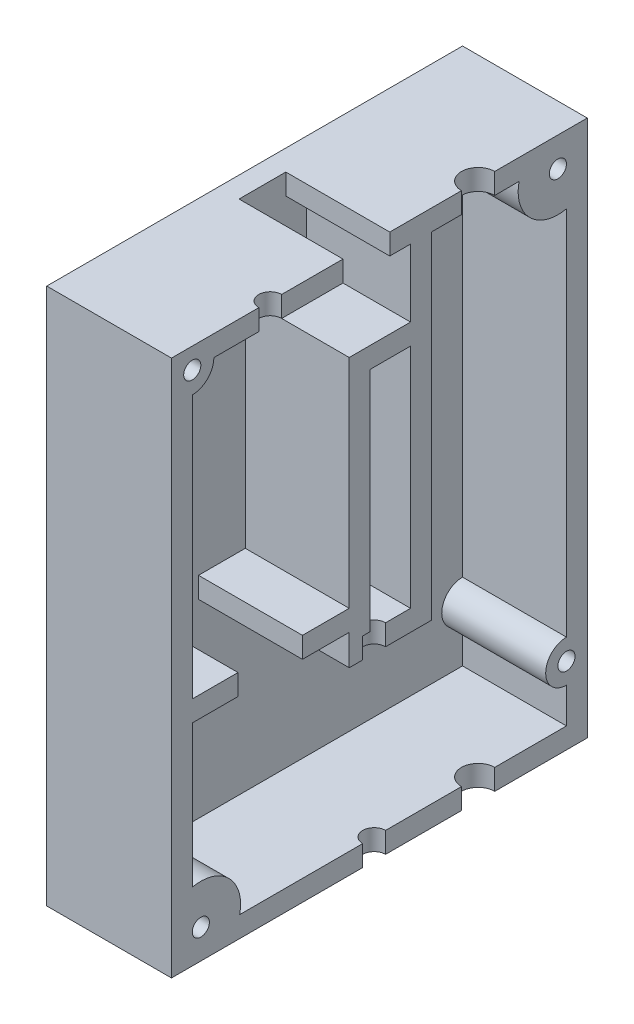
SolidWorks part; units mm, degrees
ref_plane "前视基准面" through (0, 0, 0) normal (0, 0, 1) x (1, 0, 0)
ref_plane "上视基准面" through (0, 0, 0) normal (0, 1, 0) x (1, 0, 0)
ref_plane "右视基准面" through (0, 0, 0) normal (1, 0, 0) x (0, 0, -1)
other "Configuration Table"
sketch "草图1" plane through (0, 0, 0) normal (1, 0, 0) x (0, 0, -1)
  line L1 (-20, 25.825) -> (20, 25.825)
  line L2 (-20, 25.825) -> (-20, -25.825)
  line L3 (-20, -25.825) -> (20, -25.825)
  line L4 (20, 25.825) -> (20, -25.825)
  line L5 (-20, 25.825) -> (20, -25.825) construction
  line L6 (-20, -25.825) -> (20, 25.825) construction
  point P0 (0, 0)
  dimension "D1" = 51.65
  dimension "D2" = 40
extrude "凸台-拉伸1" add sketch "草图1" along normal blind 12
shell "抽壳1" thickness 2 removed face at (12, 0, 0)
sketch "草图3" plane through (2, 0, 0) normal (1, 0, 0) x (0, 0, -1)
  line L19 (-2.9, 17.325) -> (3, 17.325)
  line L20 (-2.9, 17.325) -> (-2.9, -3.575)
  line L21 (-2.9, -8.525) -> (5, -8.525)
  line L22 (5, 17.175) -> (5, -8.525)
  line L23 (-3, 18.525) -> (-3, -3.475) construction
  line L24 (3.5, -8.725) -> (-4.5, -8.725) construction
  line L25 (8, 24.825) -> (8, -27.175) construction
  line L26 (18, 23.825) -> (-18, 23.825) construction
  line L27 (-18, 23.825) -> (-18, -23.825) construction
  line L28 (3, 23.825) -> (5, 23.825)
  line L29 (3, 23.825) -> (3, 17.325)
  line L31 (5, 23.825) -> (5, 17.175)
  line L32 (-0.9, 15.325) -> (3, 15.325)
  line L33 (-0.9, 15.325) -> (-0.9, -6.525)
  line L34 (-0.9, -6.525) -> (3, -6.525)
  line L35 (3, 15.325) -> (3, -6.525)
  line L36 (-18, -3.575) -> (-13.6, -3.575)
  line L37 (-18, -3.575) -> (-18, -5.575)
  line L38 (-18, -5.575) -> (-13.6, -5.575)
  line L39 (-13.6, -3.575) -> (-13.6, -5.575)
  line L40 (-18, -3.475) -> (-3, -3.475) construction
  line L41 (-7.4, -3.575) -> (-2.9, -3.575)
  line L42 (-7.4, -3.575) -> (-7.4, -5.575)
  line L43 (-7.4, -5.575) -> (-2.9, -5.575)
  line L45 (-7.5, -4.975) -> (-7.5, -3.475) construction
  line L46 (-13.5, -3.475) -> (-13.5, -4.975) construction
  line L48 (-2.9, -5.575) -> (-2.9, -8.525)
  dimension "D1" = 0.1
  dimension "D2" = 0.2
  dimension "D3" = 3
  dimension "D4" = 6.5
  dimension "D5" = 2
  dimension "D6" = 2
  dimension "D7" = 2
  dimension "D8" = 2
  dimension "D9" = 2
  dimension "D10" = 0.1
  dimension "D11" = 0.1
  dimension "D12" = 0.1
  dimension "D13" = 2
  dimension "D14" = 2
extrude "凸台-拉伸6" add sketch "草图3" along normal up to surface (10 mm away) up to face at (12, 0, 0)
sketch "草图4" plane through (0, 25.825, 0) normal (0, 1, 0) x (1, 0, 0)
  line L0 (2, 3) -> (2, -18) construction
  line L1 (12, 1) -> (2, 1)
  line L2 (12, 1) -> (12, -3.5)
  line L3 (12, -3.5) -> (2, -3.5)
  line L4 (2, 1) -> (2, -3.5)
  line L5 (12, -3.5) -> (22, -3.5) construction
  circle A1 centre (12, -10.5) radius 1.1
  circle A2 centre (12, 9.5) radius 1.6
  arc A3 (12, 7.9) -> (12, 11.1) centre (12, 9.5) ccw construction
  arc A4 (12, -11.6) -> (12, -9.4) centre (12, -10.5) ccw construction
extrude "切除-拉伸1" cut sketch "草图4" against normal up to next
sketch "草图5" plane through (0, -25.825, 0) normal (0, -1, 0) x (1, 0, 0)
  circle A0 centre (12, -9.5) radius 1.6
  circle A1 centre (12, 0.5) radius 1.1
  circle A2 centre (12, 0.5) radius 1 construction
  arc A3 (12, -7.9) -> (12, -11.1) centre (12, -9.5) ccw construction
  dimension "D1" = 0.1
extrude "切除-拉伸2" cut sketch "草图5" against normal blind 19.3
sketch "草图6" plane through (2, 0, 0) normal (1, 0, 0) x (0, 0, -1)
  line L0 (18, -23.825) -> (18, 23.825) construction
  line L1 (18, 23.825) -> (11.1, 23.825) construction
  line L2 (16.7315, -20.925) -> (15.49, -20.925) construction
  line L3 (20, -25.825) -> (20, 25.825) construction
  line L4 (-20, -20.4212) -> (-20, -25.825)
  line L5 (-18, -23.825) -> (-1.6, -23.825) construction
  line L6 (-20, -25.825) -> (-14.5962, -25.825)
  line L7 (-18, -5.575) -> (-18, -23.825) construction
  line L11 (-20, 23.2722) -> (-20, 24.3778)
  line L12 (-18.5528, 25.825) -> (-17.4472, 25.825)
  line L14 (-20, -25.825) -> (-1.6, -25.825) construction
  line L15 (-20, 25.825) -> (-20, -25.825) construction
  line L16 (-11.6, 25.825) -> (-20, 25.825) construction
  line L18 (14.5962, 25.825) -> (20, 25.825)
  line L19 (20, 25.825) -> (20, 20.4212)
  circle A0 centre (-17.175, -23) radius 0.825
  circle A1 centre (17.175, 23) radius 0.825
  circle A2 centre (18, -18.425) radius 0.825
  circle A3 centre (-18, 23.825) radius 0.825
  circle A5 centre (18, -18.425) radius 2
  arc A7 (-20, 23.2722) -> (-17.4472, 25.825) centre (-18, 23.825) ccw
  arc A8 (-18.5528, 25.825) -> (-20, 24.3778) centre (-18, 23.825) ccw
  arc A10 (-14.5962, -25.825) -> (-20, -20.4212) centre (-17.175, -23) ccw
  arc A11 (14.5962, 25.825) -> (20, 20.4212) centre (17.175, 23) ccw
  dimension "D1" = 1.65
  dimension "D2" = 1.65
  dimension "D3" = 1.65
  dimension "D4" = 1.65
  dimension "D6" = 3
  dimension "D7" = 3
  dimension "D8" = 1.25
  dimension "D5" = 2.5
extrude "凸台-拉伸7" add sketch "草图6" along normal up to surface (10 mm away) up to face at (12, -1.525, 13.8)
sketch "草图7" plane through (12, 0, 0) normal (1, 0, 0) x (0, 0, -1)
  line L0 (18, -19.25) -> (18, -17.6) construction
  circle A1 centre (18, -18.425) radius 0.825
  circle A3 centre (-18, 23.825) radius 0.825
  arc A5 (18, -17.6) -> (18, -19.25) centre (18, -18.425) ccw construction
  arc A7 (-18, 23) -> (-17.175, 23.825) centre (-18, 23.825) ccw construction
extrude "切除-拉伸3" cut sketch "草图7" against normal blind 2.5
sketch "草图8" plane through (2, 0, 0) normal (1, 0, 0) x (0, 0, -1)
  line L0 (-20, 25.825) -> (-15.925, 25.825)
  line L1 (-11.6, 25.825) -> (-20, 25.825) construction
  line L2 (-15.925, 25.825) -> (-15.925, 23.825)
  line L3 (-18, 21.75) -> (-20, 21.75)
  line L4 (-20, 25.825) -> (-20, -25.825) construction
  line L5 (-20, 21.75) -> (-20, 25.825)
  line L6 (18, -19.25) -> (18, -17.6) construction
  line L7 (19, -16.6929) -> (19, -20.1571)
  line L8 (20, -25.825) -> (20, 25.825) construction
  arc A0 (-18, 21.75) -> (-15.925, 23.825) centre (-18, 23.825) ccw construction
  arc A1 (-18, 21.75) -> (-15.925, 23.825) centre (-18, 23.825) ccw
  arc A2 (19, -16.6929) -> (19, -20.1571) centre (18, -18.425) ccw
  arc A3 (18, -16.425) -> (18, -20.425) centre (18, -18.425) ccw construction
  dimension "D1" = 1
extrude "凸台-拉伸8" add sketch "草图8" along normal up to surface (7.5 mm away) from surface up to face at (9.5, 23.882, 18.057) starting at face at (2, 4.4, -1.05)
